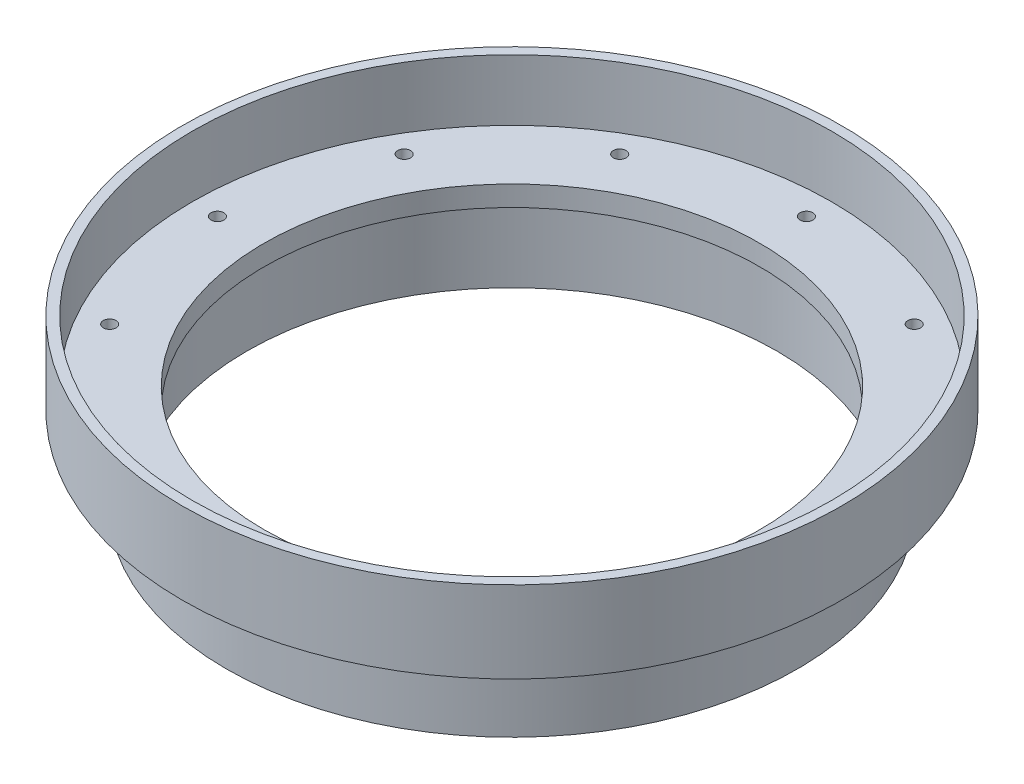
SolidWorks part; units mm, degrees
material "6061-T6 (SS)"
ref_plane "Front Plane" through (0, 0, 0) normal (0, 0, 1) x (1, 0, 0)
ref_plane "Top Plane" through (0, 0, 0) normal (0, 1, 0) x (1, 0, 0)
ref_plane "Right Plane" through (0, 0, 0) normal (1, 0, 0) x (0, 0, -1)
ref_axis "Axis1" through (0, 55, 0) along (0, -1, 0)
sketch "Cross Section" plane through (0, 0, 0) normal (0, 0, 1) x (1, 0, 0)
  line L0 (-38.608, 0) -> (-38.608, -3.175)
  line L1 (-38.608, -3.175) -> (-41.275, -3.175)
  line L2 (-41.275, -3.175) -> (-41.275, -15.875)
  line L4 (0, -15.875) -> (-38.1, -15.875) construction
  line L5 (-44.45, -15.875) -> (-44.45, -3.175)
  line L6 (-44.45, -3.175) -> (-51.308, -3.175)
  line L7 (-51.308, -3.175) -> (-51.308, 9.525)
  line L8 (-51.308, 9.525) -> (-49.784, 9.525)
  line L9 (-49.784, 9.525) -> (-49.784, 0)
  line L10 (-49.784, 0) -> (-38.608, 0)
  line L11 (-38.608, 0) -> (0, 0) construction
  line L12 (0, 55) -> (0, -55) construction
  line L13 (-44.45, -15.875) -> (-41.275, -15.875)
  line L14 (-49.784, 1.5875) -> (-49.784, 3.175) construction
  dimension "D1" = 2.667
  dimension "D3" = 3.175
  dimension "D5" = 6.858
  dimension "D6" = 12.7
  dimension "D9" = 3.175
  dimension "D8" = 38.608
revolve "Main" add sketch "Cross Section" angle 360 about axis through (0, 55, 0) along (0, -1, 0)
sketch "Hole Location" plane through (0, 0, 0) normal (0, 1, 0) x (1, 0, 0)
  line L0 (0, 0) -> (-45.847, 0) construction
  circle A0 centre (0, 0) radius 45.847 construction
  dimension "D1" = 91.694
hole_wizard "#3-48 Tapped Hole1" positions "Sketch5" profile "Sketch7" tap size "#3-48" standard "ANSI Inch"
sketch "Sketch5" plane through (0, 0, 0) normal (0, 1, 0) x (1, 0, 0)
  point P0 (-45.847, 0)
sketch "Sketch7" plane through (-45.847, 0, 0) normal (1, 0, 0) x (0, 0, 1)
  line L0 (0, 0) -> (0, 3.901)
  line L1 (0, 3.901) -> (0.9969, 3.302)
  line L2 (0.9969, 3.302) -> (0.9969, 0)
  line L5 (0.9969, 0) -> (0, 0)
  line L10 (0, 3.901) -> (-0.997, 3.302) construction
  line L11 (0, -6.35) -> (0, 107.95) construction
  dimension "Tap Drill Dia." = 1.9939
  dimension "Tap Drill Depth" = 3.302
  dimension "Drill Angle" = 118
cosmetic thread "Hole Thread1" parameters "D1"=3.175, "D2"=2.5146
pattern_circular "Screw Holes" count 12 over 360 about axis through (0, 55, 0) along (0, -1, 0) of "#3-48 Tapped Hole1"
equation "\"D8@Cross Section\"=\"TANK DIAMETER@Cryo Tank.Assembly\"/2+\"LINER COMPRESSION DELTA@Cryo Tank.Assembly\""
equation "\"D1@Hole Location\"=\"TANK DIAMETER@Cryo Tank.Assembly\"+\"GASKET SEAT THICKNESS@Cryo Tank.Assembly\"+\"LINER THICKNESS@Cryo Tank.Assembly\"+\"LINER COMPRESSION DELTA@Cryo Tank.Assembly\"+\"SHRINK FIT DELTA@Cryo Tank.Assembly\""
equation "\"D1@Cross Section\"=\"LINER THICKNESS@Cryo Tank.Assembly\"-\"LINER COMPRESSION DELTA@Cryo Tank.Assembly\""
equation "\"D3@Cross Section\"=\"ALUMINUM LAP THICKNESS@Cryo Tank.Assembly\""
equation "\"D5@Cross Section\"=2*\"CF THICKNESS@Cryo Tank.Assembly\"+\"NOMEX THICKNESS@Cryo Tank.Assembly\""
